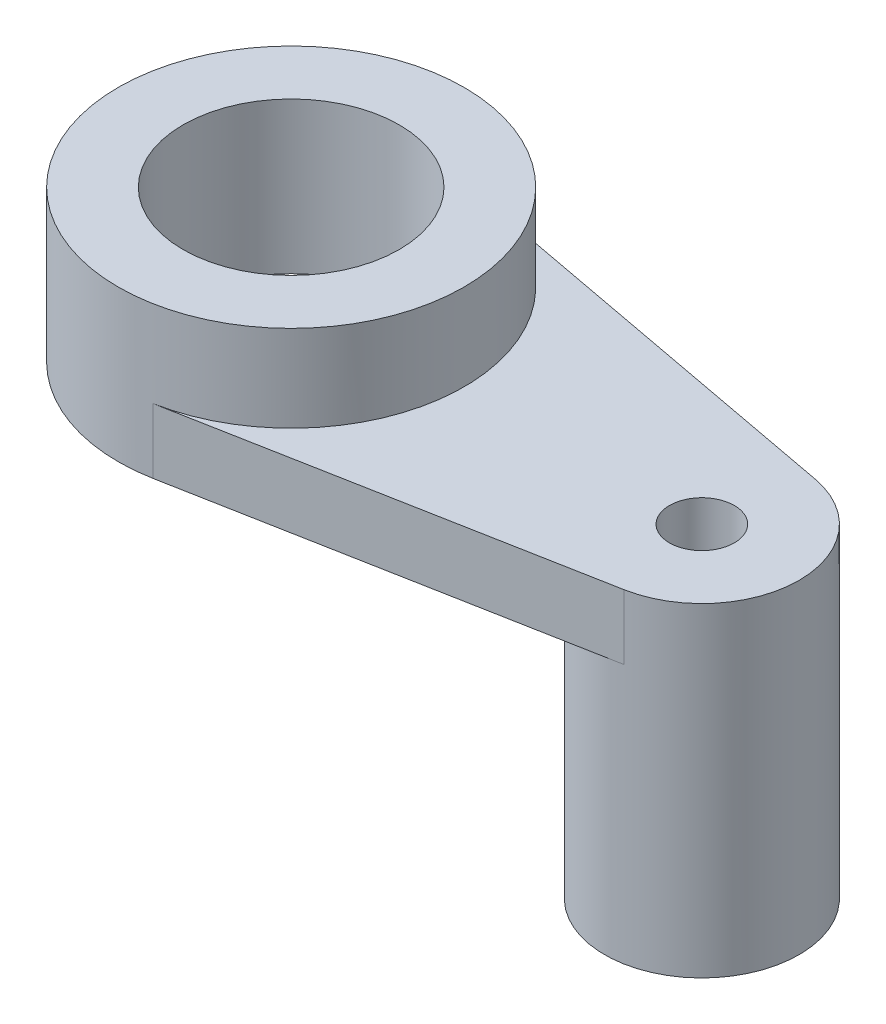
SolidWorks part; units mm, degrees
ref_plane "Płaszczyzna przednia" through (0, 0, 0) normal (0, 0, 1) x (1, 0, 0)
ref_plane "Płaszczyzna górna" through (0, 0, 0) normal (0, 1, 0) x (1, 0, 0)
ref_plane "Płaszczyzna prawa" through (0, 0, 0) normal (1, 0, 0) x (0, 0, -1)
sketch "Szkic1" plane through (0, 0, 0) normal (0, 1, 0) x (1, 0, 0)
  line L0 (2.9474, 15.7262) -> (39.6579, 8.846)
  line L1 (39.6579, -8.846) -> (2.9474, -15.7262)
  circle A0 centre (0, 0) radius 10
  circle A1 centre (38, 0) radius 3
  circle A2 centre (0, 0) radius 16
  arc A3 (39.6579, 8.846) -> (39.6579, -8.846) centre (38, 0) cw
  point P11 (0, 0)
  dimension "D1" = 20
  dimension "D3" = 6
  dimension "D5" = 9
  dimension "D4" = 38
  dimension "D2" = 6
extrude "Dodanie-wyciągnięcie2" add sketch "Szkic1" along normal blind 14 contours A2 A0 region at (11.9635, 0, -9.9296)
extrude "Dodanie-wyciągnięcie3" add sketch "Szkic1<5>" along normal blind 6 contours A3 L0 A2 L1 A1 region at (27.4093, 0, 0)
sketch "Szkic1<5>" plane through (0, 0, 0) normal (0, 1, 0) x (1, 0, 0) same geometry as "Szkic1"
sketch "Szkic2" plane through (0, 0, 0) normal (0, -1, 0) x (1, 0, 0)
  circle A0 centre (38, 0) radius 9
  arc A1 (39.6579, -8.846) -> (39.6579, 8.846) centre (38, 0) ccw construction
  arc A2 (39.6579, -8.846) -> (39.6579, 8.846) centre (38, 0) ccw
  circle A3 centre (38, 0) radius 3 construction
  circle A4 centre (38, 0) radius 3
  arc M6 (39.6579, -8.846) -> (39.6579, 8.846) centre (38, 0) ccw
  circle M8 centre (38, 0) radius 3
extrude "Dodanie-wyciągnięcie4" add sketch "Szkic2" along normal blind 24 contours A0 M6 M8 region at (44.7295, 0, -5.5854)
